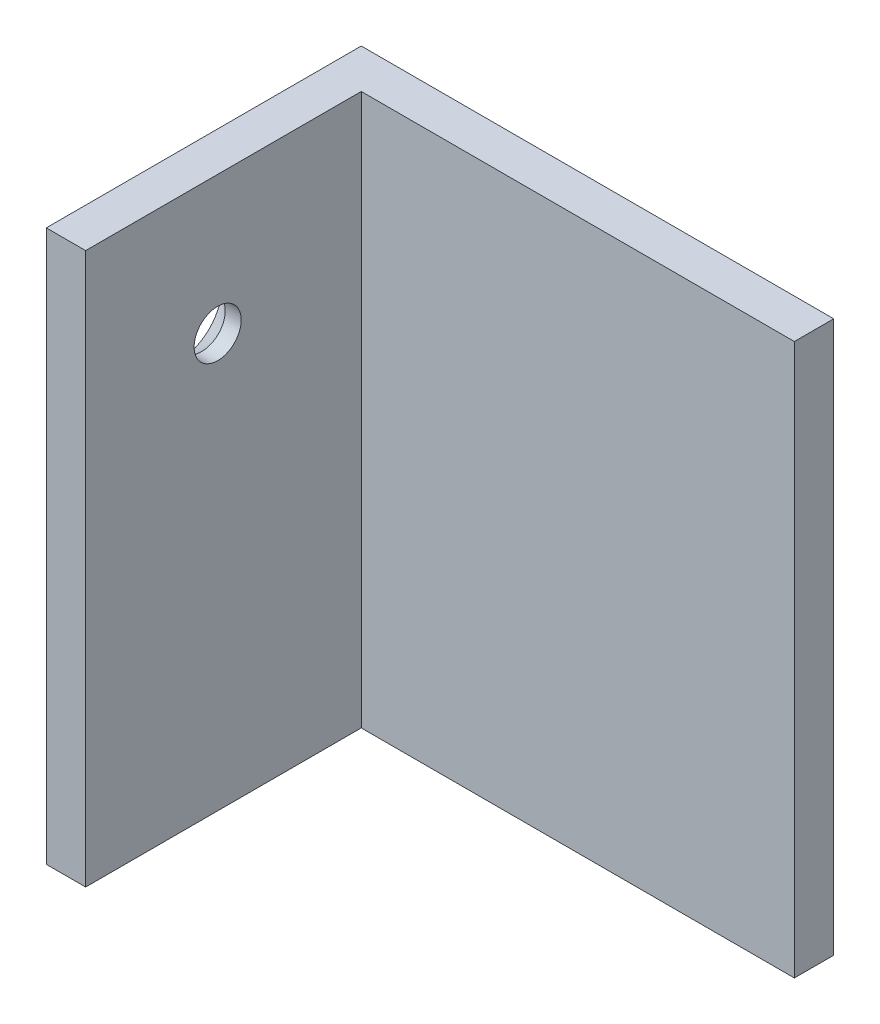
SolidWorks part; units mm, degrees
ref_plane "Front" through (0, 0, 0) normal (0, 0, 1) x (1, 0, 0)
ref_plane "Top" through (0, 0, 0) normal (0, 1, 0) x (1, 0, 0)
ref_plane "Right" through (0, 0, 0) normal (1, 0, 0) x (0, 0, -1)
sketch "Sketch1" plane through (0, 0, 0) normal (0, 1, 0) x (1, 0, 0)
  line L0 (-19.05, -12.7) -> (-15.875, -12.7)
  line L1 (-19.05, -12.7) -> (19.05, -12.7) construction
  line L2 (-19.05, -12.7) -> (-19.05, 12.7)
  line L3 (-19.05, 12.7) -> (19.05, 12.7)
  line L4 (19.05, -12.7) -> (19.05, 12.7) construction
  line L5 (-19.05, -12.7) -> (19.05, 12.7) construction
  line L6 (-19.05, 12.7) -> (19.05, -12.7) construction
  line L7 (-15.875, -12.7) -> (-15.875, 9.525)
  line L8 (-15.875, 9.525) -> (19.05, 9.525)
  line L9 (19.05, 9.525) -> (19.05, 12.7)
  point P0 (0, 0)
  point P10 (0, -12.7)
  dimension "D1" = 38.1
  dimension "D2" = 25.4
  dimension "D3" = 34.925
  dimension "D4" = 22.225
extrude "Boss-Extrude1" add sketch "Sketch1" along normal mid plane 44.45
sketch "Sketch2" plane through (-19.05, 0, 0) normal (-1, 0, 0) x (0, 0, 1)
  line L0 (-9.525, 22.225) -> (-9.525, -22.225) construction
  line L1 (-12.7, 22.225) -> (12.7, 22.225) construction
  line L2 (-12.7, -22.225) -> (12.7, -22.225) construction
  line L3 (12.7, 22.225) -> (12.7, -22.225) construction
  line L4 (-9.525, 22.225) -> (12.7, 22.225) construction
  line L5 (-9.525, 22.225) -> (-9.525, 0) construction
  line L6 (-9.525, 0) -> (12.7, 0) construction
  line L7 (12.7, 22.225) -> (12.7, 0) construction
  line L9 (-4.445, 22.225) -> (-4.445, -22.225) construction
  circle A0 centre (2.055, 11.1125) radius 2
  point P14 (12.7, 11.1125)
  dimension "D1" = 4
  dimension "D2" = 5.08
  dimension "D3" = 6.5
extrude "Cut-Extrude1" [suppressed] cut sketch "Sketch2" against normal through all
hole_wizard "CSK for #6 Flat Head Machine Screw1" positions "Sketch3" profile "Sketch5" countersink size "#6" standard "ANSI Inch" end condition through all
sketch "Sketch3" plane through (-19.05, 0, 0) normal (-1, 0, 0) x (0, 0, 1)
  point P0 (2.055, 11.1125)
sketch "Sketch5" plane through (-19.05, 11.1125, 2.055) normal (0, 1, 0) x (0, 0, 1)
  line L0 (0, 0) -> (0, 38.1)
  line L1 (0, 38.1) -> (1.8986, 38.1)
  line L2 (1.8986, 38.1) -> (1.8986, 1.892)
  line L3 (1.8986, 1.892) -> (3.5433, 0)
  line L5 (3.5433, 0) -> (0, 0)
  line L6 (-1.8986, 1.892) -> (-3.5433, 0) construction
  line L11 (0, -6.35) -> (0, 107.95) construction
  dimension "Thru Hole Dia." = 3.7973
  dimension "Thru Hole Depth" = 38.1
  dimension "Near C'Sink Dia." = 7.0866
  dimension "Near C'Sink Angle" = 82
